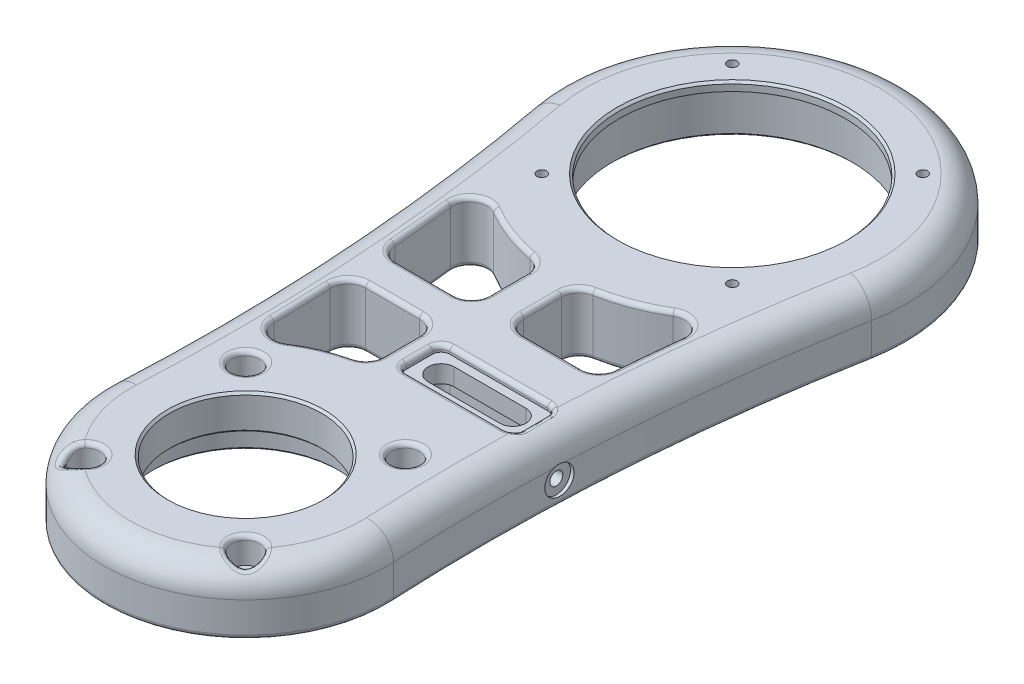
SolidWorks part; units mm, degrees
ref_plane "Front" through (0, 0, 0) normal (0, 0, 1) x (1, 0, 0)
ref_plane "Top" through (0, 0, 0) normal (0, 1, 0) x (1, 0, 0)
ref_plane "Right" through (0, 0, 0) normal (1, 0, 0) x (0, 0, -1)
sketch "Эскиз1" plane through (0, 0, 0) normal (0, 1, 0) x (1, 0, 0)
  line L0 (0, 0) -> (0, 112) construction
  line L3 (0, 0) -> (0, -109) construction
  circle A0 centre (0, 112) radius 40
  circle A1 centre (0, 0) radius 32.5
  circle A2 centre (0, -109) radius 50
  arc A3 (-48.1763, -95.6191) -> (-39.3342, 104.7321) centre (-477.8164, 23.7129) ccw
  arc A4 (39.3342, 104.7321) -> (48.1763, -95.6191) centre (477.8164, 23.7129) ccw
  dimension "D2" = 80
  dimension "D3" = 65
  dimension "D5" = 100
  dimension "D1" = 112
  dimension "D4" = 109
extrude "Бобышка-Вытянуть1" add sketch "Эскиз1" along normal blind 14 contours A2 A1 | A1 A0 | A0 region at (0, 0, -112) region at (0, 0, -52.811) region at (0, 0, 0)
sketch "Эскиз2" plane through (0, 0, 0) normal (0, 1, 0) x (1, 0, 0)
  circle A0 centre (0, 0) radius 21.1
  dimension "D1" = 42.2
extrude "Вырез-Вытянуть2" cut sketch "Эскиз2" along normal blind 6
sketch "Эскиз3" plane through (0, 0, 0) normal (0, 1, 0) x (1, 0, 0)
  circle A0 centre (0, 0) radius 17.5
  dimension "D1" = 35
extrude "Вырез-Вытянуть4" cut sketch "Эскиз3" along normal through all
sketch "Эскиз4" plane through (0, 0, 0) normal (0, 1, 0) x (1, 0, 0)
  line L0 (0, 0) -> (0, 65.2467) construction
  line L1 (0, 0) -> (-110.2485, 0) construction
  line L2 (0, 0) -> (18.3848, 18.3848) construction
  circle A0 centre (0, 0) radius 26 construction
  circle A1 centre (18.3848, 18.3848) radius 1.75
  circle A2 centre (18.3848, -18.3848) radius 1.75
  circle A3 centre (-18.3848, -18.3848) radius 1.75
  circle A4 centre (-18.3848, 18.3848) radius 1.75
  point P18 (0, 0)
  dimension "D1" = 45
  dimension "D2" = 3.5
  dimension "D3" = 52
extrude "Вырез-Вытянуть6" cut sketch "Эскиз4" along normal through all
sketch "Эскиз5" plane through (0, 0, 0) normal (0, 1, 0) x (1, 0, 0)
  circle A7 centre (0, 0) radius 26 construction
  circle A8 centre (18.3848, 18.3848) radius 3.25
  circle A9 centre (18.3848, -18.3848) radius 3.25
  circle A10 centre (-18.3848, -18.3848) radius 3.25
  circle A11 centre (-18.3848, 18.3848) radius 3.25
  point P14 (0, 0)
  dimension "D1" = 6.5
  dimension "D2" = 52
  dimension "D3" = 4
extrude "Вырез-Вытянуть7" cut sketch "Эскиз5" along normal through all from offset 8 contours A7 | A10 | A11 | A8 | A9 region at (18.3848, 0, -18.3848) region at (18.3848, 0, 18.3848) region at (-18.3848, 0, 18.3848) region at (-18.3848, 0, -18.3848)
sketch "Эскиз6" plane through (0, 0, 0) normal (0, 1, 0) x (1, 0, 0)
  line L0 (0, 0) -> (0, 112) construction
  circle A1 centre (0, 112) radius 26
  circle A2 centre (0, 112) radius 27.6
  circle A3 centre (0, 112) radius 35.5
  dimension "D1" = 52
  dimension "D2" = 71
  dimension "D3" = 55.2
extrude "Вырез-Вытянуть8" cut sketch "Эскиз6" along normal through all contours A1 region at (0, 0, -112)
extrude "Вырез-Вытянуть9" cut sketch "Эскиз6<4>" along normal blind 2 contours A3
sketch "Эскиз6<4>" plane through (0, 0, 0) normal (0, 1, 0) x (1, 0, 0) same geometry as "Эскиз6"
extrude "Вырез-Вытянуть10" cut sketch "Эскиз6<5>" along normal blind 12 contours A2
sketch "Эскиз6<5>" plane through (0, 0, 0) normal (0, 1, 0) x (1, 0, 0) same geometry as "Эскиз6"
sketch "Эскиз7" plane through (0, 0, 0) normal (0, 1, 0) x (1, 0, 0)
  line L0 (0, 0) -> (0, 40)
  line L1 (0, 40) -> (5, 40)
  line L2 (0, 40) -> (21.5, 40)
  line L5 (5, 37) -> (21.5, 37)
  line L6 (5, 43) -> (21.5, 43)
  line L7 (21.5, 40) -> (26.5, 40)
  line L8 (26.5, 40) -> (26.5, 43)
  line L9 (24.5, 45) -> (2, 45)
  line L10 (0, 43) -> (0, 37)
  line L11 (2, 35) -> (24.5, 35)
  line L12 (26.5, 37) -> (26.5, 40)
  arc A0 (5, 43) -> (5, 37) centre (5, 40) ccw
  arc A1 (21.5, 37) -> (21.5, 43) centre (21.5, 40) ccw
  arc A5 (24.5, 45) -> (26.5, 43) centre (24.5, 43) cw
  arc A6 (26.5, 37) -> (24.5, 35) centre (24.5, 37) cw
  arc A7 (2, 35) -> (0, 37) centre (2, 37) cw
  arc A8 (2, 45) -> (0, 43) centre (2, 43) ccw
  dimension "D4" = 16.5
  dimension "D3" = 3
  dimension "D5" = 2
  dimension "D1" = 40
  dimension "D2" = 21.5
  dimension "D6" = 5
extrude "Вырез-Вытянуть11" cut sketch "Эскиз7" along normal through all contours L5 A1 L6 A0 | L5 A1 L7 L2 L1 A0 region at (13.25, 0, -41.4496) region at (13.25, 0, -38.5504)
extrude "Вырез-Вытянуть12" cut sketch "Эскиз7<3>" along normal blind 8.5 contours A0 L6 A1 L5 | L5 A1 L7 L2 L1 A0 | A7 L11 A6 L12 L7 A1 L5 A0 L0 | L7 A1 L6 A0 L1 L2 region at (13.25, 0, -36.557) region at (13.25, 0, -43.443) region at (13.25, 0, -41.4496) region at (13.25, 0, -38.5504)
sketch "Эскиз7<3>" plane through (0, 0, 0) normal (0, 1, 0) x (1, 0, 0) same geometry as "Эскиз7"
extrude "Вырез-Вытянуть13" cut sketch "Эскиз7<4>" along normal through all from offset 12.5 contours A0 L6 A1 L5 | L5 A1 L7 L2 L1 A0 | L7 A1 L6 A0 L1 L2 | A7 L11 A6 L12 L7 A1 L5 A0 L0 region at (13.25, 0, -36.557) region at (13.25, 0, -43.443) region at (13.25, 0, -41.4496) region at (13.25, 0, -38.5504)
sketch "Эскиз7<4>" plane through (0, 0, 0) normal (0, 1, 0) x (1, 0, 0) same geometry as "Эскиз7"
sketch "Эскиз8" plane through (0, 0, 0) normal (1, 0, 0) x (0, 0, -1)
  line L0 (0, 0) -> (40, 0)
  line L1 (50, 0) -> (-50, 0) construction
  line L2 (40, 0) -> (40, 5)
  line L4 (43.2909, 5) -> (41.6454, 7.85)
  line L5 (41.6454, 7.85) -> (38.3546, 7.85)
  line L6 (38.3546, 7.85) -> (36.7091, 5)
  line L7 (36.7091, 5) -> (38.3546, 2.15)
  line L8 (38.3546, 2.15) -> (41.6454, 2.15)
  line L9 (41.6454, 2.15) -> (43.2909, 5)
  circle A0 centre (40, 5) radius 1.5
  circle A1 centre (40, 5) radius 2.85 construction
  circle A2 centre (40, 5) radius 3.25
  dimension "D1" = 40
  dimension "D2" = 5
extrude "Вырез-Вытянуть14" cut sketch "Эскиз8" along normal through all from offset 20 contours A0
extrude "Вырез-Вытянуть15" cut sketch "Эскиз8<3>" against normal blind 10 from offset 29 contours L4 L5 L6 L7 L8 L9
sketch "Эскиз8<3>" plane through (0, 0, 0) normal (1, 0, 0) x (0, 0, -1) same geometry as "Эскиз8"
extrude "Вырез-Вытянуть16" cut sketch "Эскиз8<4>" along normal through all from offset 31.5 contours A2
sketch "Эскиз8<4>" plane through (0, 0, 0) normal (1, 0, 0) x (0, 0, -1) same geometry as "Эскиз8"
fillet "Скругление1" radius 1 4 edges at (0, 0, -152) (-32.8994, 0, -53.3714) (0, 0, 32.5) (32.8994, 0, -53.3714)
fillet "Скругление2" radius 6 4 edges at (0, 14, -152) (-32.8994, 14, -53.3714) (0, 14, 32.5) (32.8994, 14, -53.3714)
chamfer "Фаска1" distance 0.5 angle 45 5 edges at (0, 2, -84.4) (0, 14, 17.5) (0, 6, 17.5) (0, 0, 21.1) (0, 14, -86)
fillet "Скругление3" radius 1 6 edges at (-21.0279, 13.3526, 20.276) (20.276, 13.3526, 21.0279) (-16.0867, 14, 16.0867) (16.0867, 14, 16.0867) (18.3848, 14, -15.1348) (-18.3848, 14, -15.1348)
sketch "Эскиз9" plane through (0, 0, 0) normal (0, 1, 0) x (1, 0, 0)
  line L0 (0, 112) -> (21.9203, 133.9203) construction
  line L2 (20.2057, 135.635) -> (19.5781, 133.2927)
  line L3 (19.5781, 133.2927) -> (21.2927, 131.5781)
  line L4 (21.2927, 131.5781) -> (23.635, 132.2057)
  line L5 (23.635, 132.2057) -> (24.2626, 134.5479)
  line L6 (24.2626, 134.5479) -> (22.5479, 136.2626)
  line L7 (22.5479, 136.2626) -> (20.2057, 135.635)
  circle A0 centre (0, 112) radius 31 construction
  circle A1 centre (21.9203, 133.9203) radius 1.1
  circle A2 centre (21.9203, 133.9203) radius 2.1 construction
  dimension "D1" = 62
  dimension "D2" = 4.2
  dimension "D3" = 2.2
extrude "Вырез-Вытянуть18" cut sketch "Эскиз9" along normal through all contours A1 region at (21.9203, 0, -133.9203)
extrude "Вырез-Вытянуть19" cut sketch "Эскиз9<3>" along normal blind 11
sketch "Эскиз9<3>" plane through (0, 0, 0) normal (0, 1, 0) x (1, 0, 0) same geometry as "Эскиз9"
pattern_circular "Круговой массив1" count 4 over 360 about axis through (0, 12, -112) along (0, -1, 0) of "Вырез-Вытянуть19", "Вырез-Вытянуть18"
sketch "Эскиз11" plane through (0, 0, 0) normal (0, 1, 0) x (1, 0, 0)
  line L0 (0, 0) -> (0, 112) construction
  line L1 (0, 0) -> (0, -109) construction
  line L2 (4, 0) -> (4, 112)
  line L3 (-4, 0) -> (-4, 112)
  line L4 (-49.8114, 52) -> (68.764, 52)
  line L5 (-49.8114, 48) -> (68.764, 48)
  line L6 (-49.8114, 56) -> (68.764, 56)
  circle A0 centre (0, 112) radius 40
  circle A1 centre (0, 0) radius 32.5
  circle A2 centre (0, -109) radius 50
  arc A3 (-48.1763, -95.6191) -> (-39.3342, 104.7321) centre (-477.8164, 23.7129) ccw
  arc A4 (39.3342, 104.7321) -> (48.1763, -95.6191) centre (477.8164, 23.7129) ccw
  arc A5 (-40.4681, -97.7601) -> (-31.4673, 106.1857) centre (-477.8164, 23.7129) ccw
  arc A7 (31.4673, 106.1857) -> (40.4681, -97.7601) centre (477.8164, 23.7129) ccw
  dimension "D2" = 80
  dimension "D3" = 65
  dimension "D5" = 100
  dimension "D1" = 112
  dimension "D4" = 109
  dimension "D10" = 52
  dimension "D6" = 8
  dimension "D7" = 4
  dimension "D8" = 8
  dimension "D9" = 4
  dimension "D11" = 4
  dimension "D12" = 4
extrude "Вырез-Вытянуть20" cut sketch "Эскиз11" along normal through all contours A5 L6 L3 A0 | A7 A0 L2 L6 | A5 A1 L3 L5 region at (-14.9305, 0, -38.1453) region at (16.0421, 0, -66.3771) region at (-16.0421, 0, -66.3771)
fillet "Скругление4" radius 4 12 edges at (-4, 7, -48) (-4, 7, -32.2529) (-23.9152, 7, -22.0072) (-24.5622, 7, -48) (4, 7, -72.2005) (4, 7, -56) (25.0617, 7, -56) (27.8369, 7, -83.2753) (-27.8369, 7, -83.2753) (-25.0617, 7, -56) (-4, 7, -56) (-4, 7, -72.2005)
fillet "Скругление5" radius 1 48 edges at (-24.0661, 0, -57.0616) (-14.676, 0, -56) (-5.1716, 0, -57.1716) (-4, 0, -64.3667) (-4.9252, 0, -71.2918) (-14.1911, 0, -74.602) (-24.8737, 0, -77.6865) (-23.252, 14, -46.7651) (-14.1808, 14, -48) (-5.1716, 14, -46.8284) (-4, 14, -39.8062) (-4.877, 14, -33.1132) (-12.6512, 14, -29.9366) (-21.8406, 14, -27.0249) (24.0661, 14, -57.0616) (25.9602, 14, -66.7847) (24.8737, 14, -77.6865) (14.1911, 14, -74.602) (4.9252, 14, -71.2918) (4, 14, -64.3667) (5.1716, 14, -57.1716) (-5.1716, 14, -57.1716) (-4, 14, -64.3667) (-4.9252, 14, -71.2918) (-14.1911, 14, -74.602) (-24.8737, 14, -77.6865) (-25.9602, 14, -66.7847) (-24.0661, 14, -57.0616) (-4.877, 0, -33.1132) (-4, 0, -39.8062) (-5.1716, 0, -46.8284) (-14.1808, 0, -48) (-23.252, 0, -46.7651) (-24.1112, 0, -37.1614) (-21.8406, 0, -27.0249) (-25.9602, 0, -66.7847) (-24.1112, 14, -37.1614) (14.676, 14, -56) (-14.676, 14, -56) (-12.6512, 0, -29.9366) (4.9252, 0, -71.2918) (4, 0, -64.3667) (5.1716, 0, -57.1716) (14.676, 0, -56) (24.0661, 0, -57.0616) (25.9602, 0, -66.7847) (24.8737, 0, -77.6865) (14.1911, 0, -74.602)
fillet "Скругление6" radius 1 18 edges at (13.25, 0, -45) (25.9142, 0, -44.4142) (26.5, 0, -40) (25.9142, 0, -35.5858) (13.25, 0, -35) (0.5858, 0, -35.5858) (0, 0, -40) (0.5858, 14, -44.4142) (13.25, 14, -45) (25.6204, 14, -44.6567) (26.3929, 13.9923, -36.3543) (25.3743, 14, -35.2012) (13.25, 14, -35) (0.5858, 14, -35.5858) (0.5858, 0, -44.4142) (0, 14, -40)
fillet "Скругление7" radius 1 1 edges at (0, 0, -76.5)
